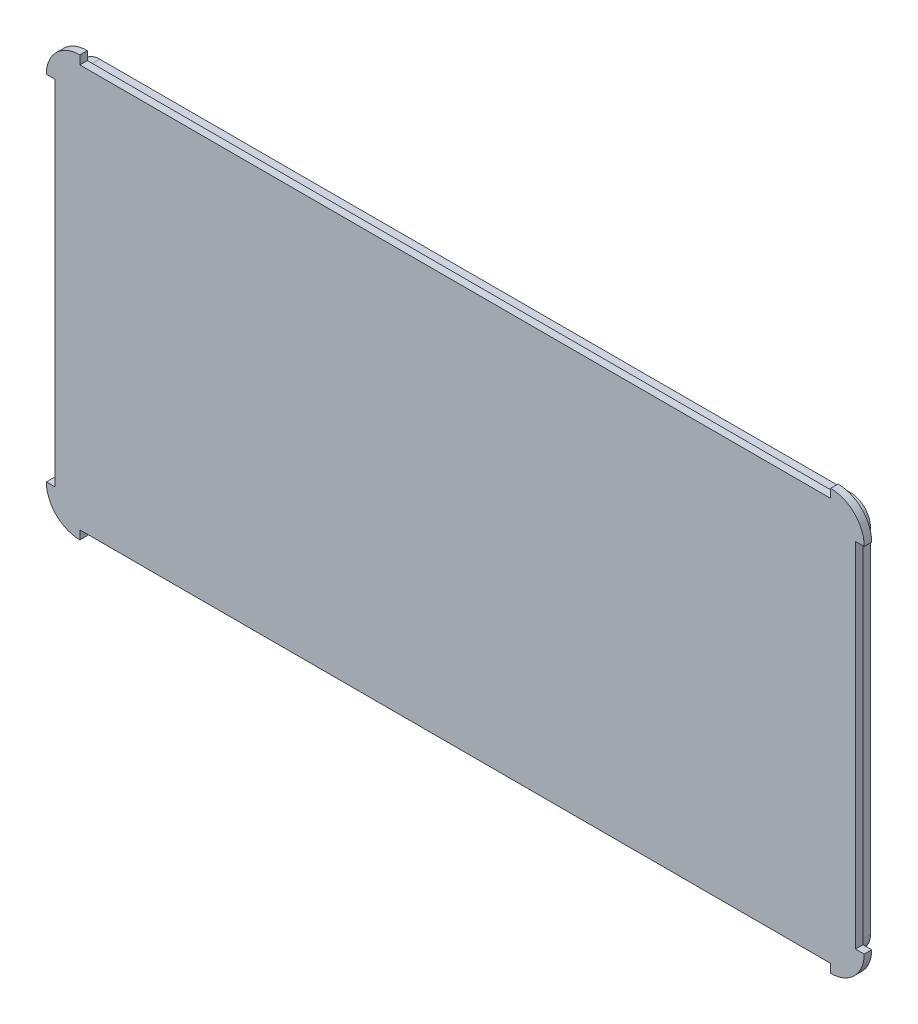
SolidWorks part; units mm, degrees
material "Стекло кварцевое прозрачное"
ref_plane "Спереди" through (0, 0, 0) normal (0, 0, 1) x (1, 0, 0)
ref_plane "Сверху" through (0, 0, 0) normal (0, 1, 0) x (1, 0, 0)
ref_plane "Справа" through (0, 0, 0) normal (1, 0, 0) x (0, 0, -1)
sketch "Sketch3" plane through (0, 0, 0) normal (0, 0, 1) x (1, 0, 0)
  line L4 (-161, 0) -> (161, 0) construction
  line L12 (0, 81) -> (0, -81) construction
  line L13 (-151, 81) -> (151, 81)
  line L14 (-161, 71) -> (-161, -71)
  line L15 (-151, -81) -> (151, -81)
  line L24 (161, 71) -> (161, -71)
  line L25 (-161, 81) -> (161, -81) construction
  line L26 (-161, -81) -> (161, 81) construction
  arc A12 (151, -81) -> (161, -71) centre (151, -71) ccw
  arc A13 (151, 81) -> (161, 71) centre (151, 71) cw
  arc A14 (-161, -71) -> (-151, -81) centre (-151, -71) ccw
  arc A15 (-151, 81) -> (-161, 71) centre (-151, 71) ccw
  point P0 (0, 0)
  dimension "D4" = 10
  dimension "D2" = 322
  dimension "D3" = 162
extrude "Boss-Extrude2" add sketch "Sketch3" against normal blind 3
sketch "Эскиз1" plane through (0, 0, -3) normal (0, 0, -1) x (-1, 0, 0)
  line L8 (-151, -79) -> (151, -79)
  line L9 (159, -71) -> (159, 71)
  line L10 (151, 79) -> (-151, 79)
  line L11 (-159, 71) -> (-159, -71)
  line L12 (-151, -79) -> (151, -79)
  line L13 (159, -71) -> (159, 71)
  line L14 (151, 79) -> (-151, 79)
  line L15 (-159, 71) -> (-159, -71)
  arc A8 (-159, -71) -> (-151, -79) centre (-151, -71) ccw
  arc A9 (151, -79) -> (159, -71) centre (151, -71) ccw
  arc A10 (159, 71) -> (151, 79) centre (151, 71) ccw
  arc A11 (-151, 79) -> (-159, 71) centre (-151, 71) ccw
  arc A12 (-159, -71) -> (-151, -79) centre (-151, -71) ccw
  arc A13 (151, -79) -> (159, -71) centre (151, -71) ccw
  arc A14 (159, 71) -> (151, 79) centre (151, 71) ccw
  arc A15 (-151, 79) -> (-159, 71) centre (-151, 71) ccw
  dimension "D1" = 2
extrude "Бобышка-Вытянуть1" add sketch "Эскиз1" along normal blind 5
sketch "Эскиз2" plane through (0, 0, 0) normal (0, 0, 1) x (1, 0, 0)
  line L2 (-164.5, 71) -> (-151, 71)
  line L3 (-151, 84.5) -> (-151, 71)
  line L5 (0, 105.4581) -> (0, -106.2128) construction
  line L6 (-173.7104, 0) -> (184.3927, 0) construction
  line L9 (164.5, -71) -> (151, -71)
  line L10 (151, -84.5) -> (151, -71)
  line L11 (-151, -84.5) -> (-151, -71)
  line L12 (-164.5, -71) -> (-151, -71)
  line L13 (151, 84.5) -> (151, 71)
  line L14 (164.5, 71) -> (151, 71)
  arc A1 (-164.5, 71) -> (-151, 84.5) centre (-151, 71) cw
  arc A3 (164.5, -71) -> (151, -84.5) centre (151, -71) cw
  arc A4 (-164.5, -71) -> (-151, -84.5) centre (-151, -71) ccw
  arc A6 (164.5, 71) -> (151, 84.5) centre (151, 71) ccw
extrude "Бобышка-Вытянуть2" add sketch "Эскиз2" against normal up to surface (3 mm away) up to face at (0, 0, -3)
equation "\"длина стекла\"=321 + 1"
equation "\"ширина стекла\"=161 + 1"
equation "\"D2@Sketch3\"=\"длина стекла\""
equation "\"D3@Sketch3\"=\"ширина стекла\""
